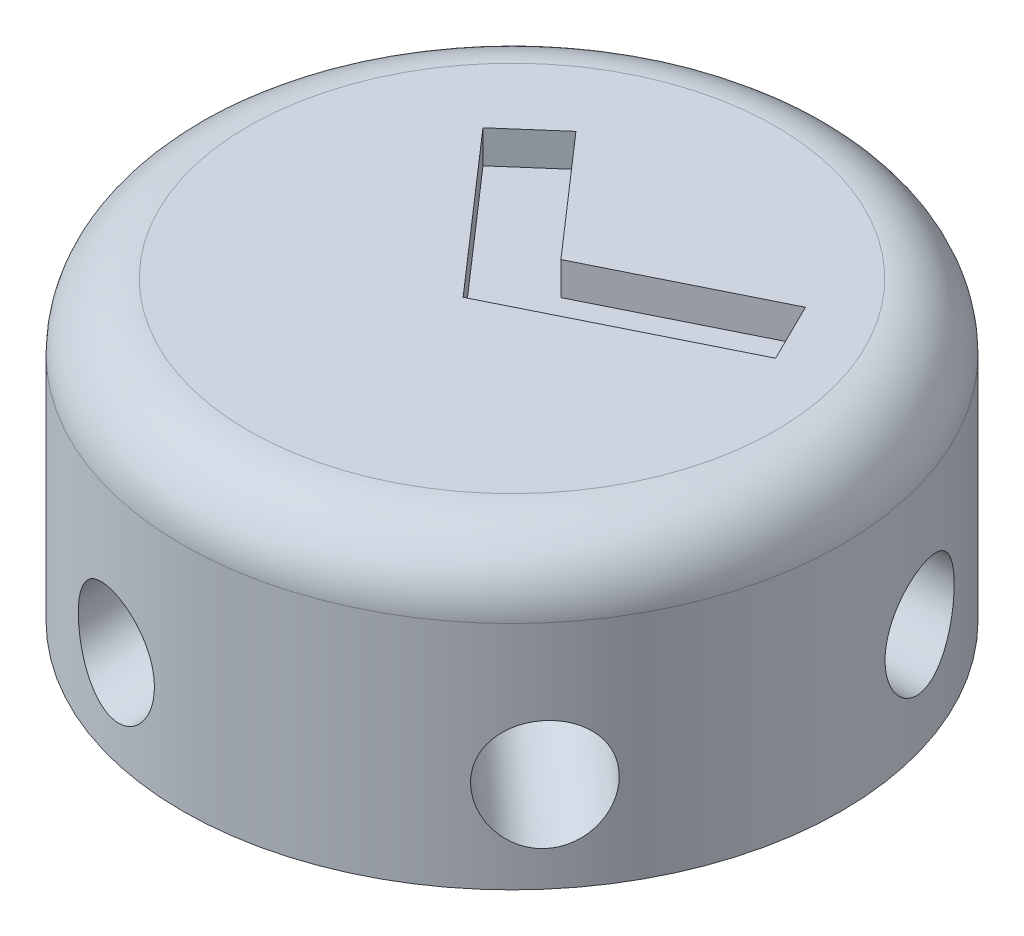
SolidWorks part; units mm, degrees
ref_plane "Front Plane" through (0, 0, 0) normal (0, 0, 1) x (1, 0, 0)
ref_plane "Top Plane" through (0, 0, 0) normal (0, 1, 0) x (1, 0, 0)
ref_plane "Right Plane" through (0, 0, 0) normal (1, 0, 0) x (0, 0, -1)
sketch "Sketch1" plane through (0, 0, 0) normal (0, 1, 0) x (1, 0, 0)
  circle A0 centre (0, 0) radius 10
  dimension "D1" = 20
extrude "base" add sketch "Sketch1" along normal blind 3 and the other way blind 6
ref_axis "6hubaxis" through (0, 5.5, 0) along (0, -1, 0)
ref_plane "Plane1" through (2.6705, -1.0931, 2.7701) normal (-0.6676, 0.2733, -0.6925) x (-0.6559, 0.2243, 0.7208)
sketch "Sketch2" [suppressed] plane through (2.6705, -1.0931, 2.7701) normal (-0.6676, 0.2733, -0.6925) x (-0.6559, 0.2243, 0.7208)
  circle A0 centre (0, 0) radius 1.5 construction
  circle A1 centre (0, 0) radius 1.5
extrude "hole1" [suppressed] cut sketch "Sketch2" against normal through all
pattern_circular "hole1mirror" [suppressed] count 2 over 360 about axis through (0, 5.5, 0) along (0, -1, 0) of bodies 112
ref_plane "Plane2" through (-0.9417, -1.2361, 3.6858) normal (0.2354, 0.309, -0.9215) x (-0.9719, 0.0738, -0.2235)
sketch "Sketch3" plane through (-0.9417, -1.2361, 3.6858) normal (0.2354, 0.309, -0.9215) x (-0.9719, 0.0738, -0.2235)
  circle A0 centre (0, 0) radius 1.5 construction
  circle A1 centre (0, 0) radius 1.5 construction
  circle A2 centre (0, 0) radius 1.6
  dimension "D1" = 3.2
extrude "hole2" cut sketch "Sketch3" against normal through all
pattern_circular "hole2mirror" count 2 over 360 about axis through (0, 5.5, 0) along (0, -1, 0) of "hole2"
ref_plane "Plane3" through (-3.7178, -1.2361, 0.8061) normal (0.9295, 0.309, -0.2015) x (-0.1912, -0.0636, -0.9795)
sketch "Sketch4" plane through (-3.7178, -1.2361, 0.8061) normal (0.9295, 0.309, -0.2015) x (-0.1912, -0.0636, -0.9795)
  circle A0 centre (0, 0) radius 1.5 construction
  circle A1 centre (0, 0) radius 1.5 construction
  circle A2 centre (0, 0) radius 1.6
  dimension "D1" = 3.2
extrude "hole3" cut sketch "Sketch4" against normal through all
pattern_circular "hole3mirror" [suppressed] count 2 over 360 about axis through (0, 5.5, 0) along (0, -1, 0) of bodies 117
ref_plane "Plane4" through (3.672, -1.0931, -1.1497) normal (-0.918, 0.2733, 0.2874) x (0.2755, -0.082, 0.9578)
sketch "Sketch5" plane through (3.672, -1.0931, -1.1497) normal (-0.918, 0.2733, 0.2874) x (0.2755, -0.082, 0.9578)
  circle A0 centre (0, 0) radius 1.5 construction
  circle A1 centre (0, 0) radius 1.5 construction
  circle A2 centre (0, 0) radius 1.6
  dimension "D1" = 3.2
extrude "Cut-Extrude1" cut sketch "Sketch5" against normal through all
ref_plane "Plane5" through (2.8756, -1.2361, 2.4906) normal (-0.7189, 0.309, -0.6227) x (-0.572, 0.2459, 0.7825)
sketch "Sketch6" plane through (2.8756, -1.2361, 2.4906) normal (-0.7189, 0.309, -0.6227) x (-0.572, 0.2459, 0.7825)
  circle A0 centre (0, 0) radius 1.5 construction
  circle A1 centre (0, 0) radius 1.5 construction
  circle A2 centre (0, 0) radius 1.6
  dimension "D1" = 3.2
extrude "Cut-Extrude2" cut sketch "Sketch6" against normal through all
ref_plane "Plane6" through (-2.6705, -1.0931, -2.7701) normal (0.6676, 0.2733, 0.6925) x (0.7445, -0.2451, -0.621)
sketch "Sketch7" plane through (-2.6705, -1.0931, -2.7701) normal (0.6676, 0.2733, 0.6925) x (0.7445, -0.2451, -0.621)
  circle A0 centre (0, 0) radius 1.5 construction
  circle A1 centre (0, 0) radius 1.5 construction
  circle A2 centre (0, 0) radius 1.6
  dimension "D1" = 3.2
extrude "Cut-Extrude3" cut sketch "Sketch7" against normal through all
sketch "Sketch8" plane through (0, -6, 0) normal (0, -1, 0) x (1, 0, 0)
  circle A0 centre (0, 0) radius 5
extrude "Boss-Extrude1" [suppressed] add sketch "Sketch8" along normal blind 2
fillet "Fillet1" radius 2 1 edges at (0, 3, 10)
sketch "Sketch9" plane through (0, 3, 0) normal (0, 1, 0) x (1, 0, 0)
  line L0 (0, 0) -> (5.6543, 2.7985)
  line L1 (0, 0) -> (-3.6468, 4.1765)
  point P3 (0, 0)
  point P5 (0, 0)
extrude "Cut-Extrude-Thin1" cut sketch "Sketch9" against normal blind 1 thin thin type mid plane wall 2
